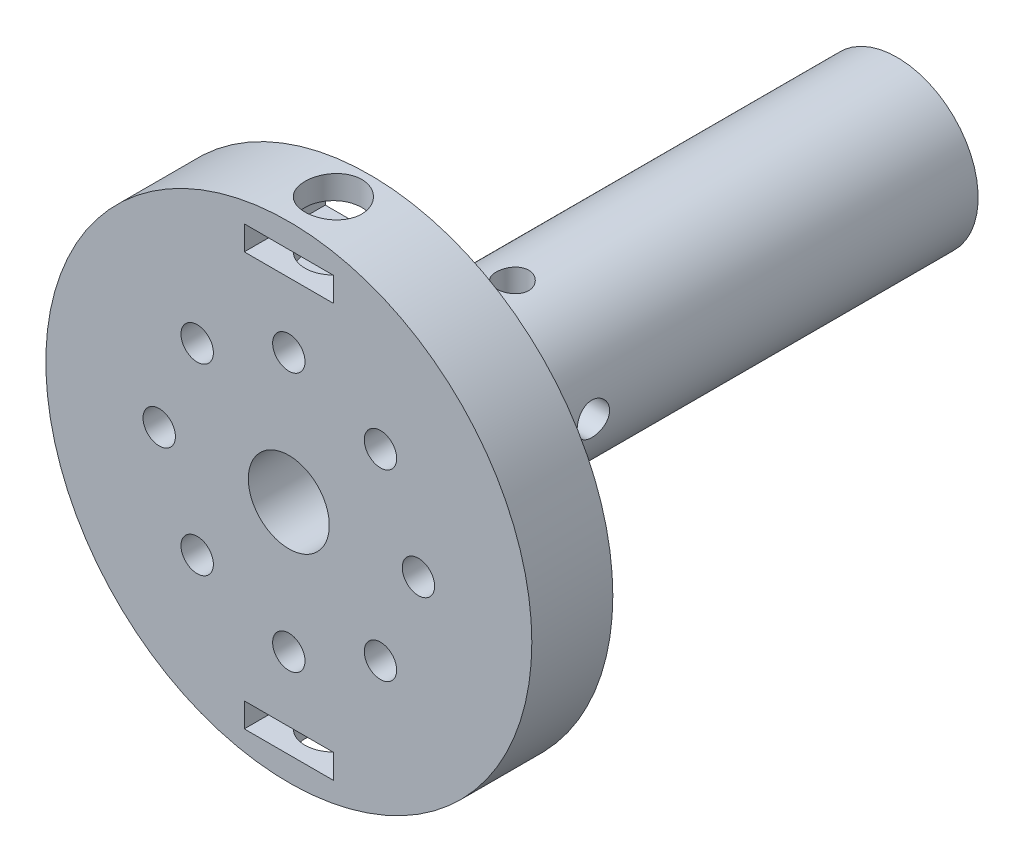
SolidWorks part; units mm, degrees
ref_plane "Front Plane" through (0, 0, 0) normal (0, 0, 1) x (1, 0, 0)
ref_plane "Top Plane" through (0, 0, 0) normal (0, 1, 0) x (1, 0, 0)
ref_plane "Right Plane" through (0, 0, 0) normal (1, 0, 0) x (0, 0, -1)
sketch "Sketch1" plane through (0, 0, 0) normal (0, 0, 1) x (1, 0, 0)
  circle A0 centre (0, 0) radius 30
  dimension "D1" = 60
extrude "Boss-Extrude1" add sketch "Sketch1" along normal blind 10
sketch "Sketch2" plane through (0, 0, 0) normal (0, 0, -1) x (-1, 0, 0)
  circle A0 centre (0, 0) radius 10
  dimension "D1" = 20
extrude "Boss-Extrude2" add sketch "Sketch2" along normal blind 65.1
extrude "Boss-Extrude3" add sketch "Sketch2<2>" along normal blind 20
sketch "Sketch2<2>" plane through (0, 0, 0) normal (0, 0, -1) x (-1, 0, 0) same geometry as "Sketch2"
sketch "Sketch5" plane through (0, 0, -65.1) normal (0, 0, -1) x (-1, 0, 0)
  circle A0 centre (0, 0) radius 5
  dimension "D1" = 10
extrude "Cut-Extrude1" cut sketch "Sketch5" against normal through all
sketch "Sketch6" plane through (0, 0, 0) normal (0, 1, 0) x (1, 0, 0)
  line L1 (30, 0) -> (-30, 0) construction
  circle A0 centre (0, 17.6) radius 2
  dimension "D1" = 4
  dimension "D2" = 17.6
extrude "Cut-Extrude2" cut sketch "Sketch6" against normal through all both and the other way through all
pattern_circular "CirPattern1" count 2 every 90 about axis through (0, 0, -65.1) along (0, 0, 1) of "Cut-Extrude2"
sketch "Sketch7" plane through (0, 0, 10) normal (0, 0, 1) x (1, 0, 0)
  circle A0 centre (0, 16) radius 2
  circle A1 centre (11.3137, 11.3137) radius 2
  circle A2 centre (16, 0) radius 2
  circle A3 centre (11.3137, -11.3137) radius 2
  circle A4 centre (0, -16) radius 2
  circle A5 centre (-11.3137, -11.3137) radius 2
  circle A6 centre (-16, 0) radius 2
  circle A7 centre (-11.3137, 11.3137) radius 2
  point P20 (0, 0)
  dimension "D1" = 4
  dimension "D2" = 16
  dimension "D3" = 8
extrude "Cut-Extrude3" cut sketch "Sketch7" against normal through all and the other way through all
sketch "Sketch9" plane through (0, 0, 0) normal (0, 0, -1) x (-1, 0, 0)
  line L0 (0, 0) -> (0, 30) construction
  line L3 (-5.5, 24) -> (5.5, 24)
  line L4 (-5.5, 24) -> (-5.5, 27)
  line L5 (-5.5, 27) -> (5.5, 27)
  line L6 (5.5, 24) -> (5.5, 27)
  line L7 (-5.5, 24) -> (5.5, 27) construction
  line L8 (-5.5, 27) -> (5.5, 24) construction
  circle A0 centre (0, 0) radius 30 construction
  point P6 (0, 25.5)
  dimension "D1" = 11
  dimension "D2" = 3
  dimension "D3" = 24
extrude "Cut-Extrude5" cut sketch "Sketch9" against normal blind 10
mirror "Mirror1" about plane through (0, 0, 0) normal (0, 1, 0) of "Cut-Extrude5"
ref_plane "Plane1" through (0, -30, 0) normal (0, -1, 0) x (-1, 0, 0)
sketch "Sketch10" plane through (0, -30, 0) normal (0, -1, 0) x (-1, 0, 0)
  line L1 (0, -1) -> (1.1394, -1) construction
  line L2 (30, 0) -> (-30, 0) construction
  circle A0 centre (0, -4.5) radius 3.5
  dimension "D1" = 7
  dimension "D2" = 1
  dimension "D3" = 3.5
extrude "Cut-Extrude6" cut sketch "Sketch10" against normal blind 8
mirror "Mirror2" about plane through (0, 0, 0) normal (0, 1, 0) of "Cut-Extrude6"
sketch "Sketch15" plane through (0, 0, 0) normal (0, 1, 0) x (1, 0, 0)
  line L0 (-30.0139, 40.1) -> (35.3147, 40.1) construction
  line L1 (10, 65.1) -> (-10, 65.1) construction
  dimension "D1" = 25
ref_plane "Plane3" through (0, 0, -40.1) normal (0, 0, -1) x (-1, 0, 0)
sketch "Sketch17" plane through (0, 0, -40.1) normal (0, 0, -1) x (-1, 0, 0)
  circle A0 centre (0, 0) radius 7.3556
extrude "Boss-Extrude4" add sketch "Sketch17" along normal blind 25
sketch "Sketch18" plane through (0, 0, -65.1) normal (0, 0, -1) x (-1, 0, 0)
  circle A0 centre (0, 0) radius 3
  dimension "D1" = 6
extrude "Cut-Extrude7" cut sketch "Sketch18" against normal blind 15
sketch "Sketch19" plane through (0, 0, -50.1) normal (0, 0, -1) x (-1, 0, 0)
  line L0 (0, 0) -> (0, 2.5) construction
  line L1 (1.6583, 2.5) -> (-1.6583, 2.5)
  arc A0 (1.6583, 2.5) -> (-1.6583, 2.5) centre (0, 0) ccw
  dimension "D1" = 2.5
extrude "Boss-Extrude5" add sketch "Sketch19" along normal blind 10
